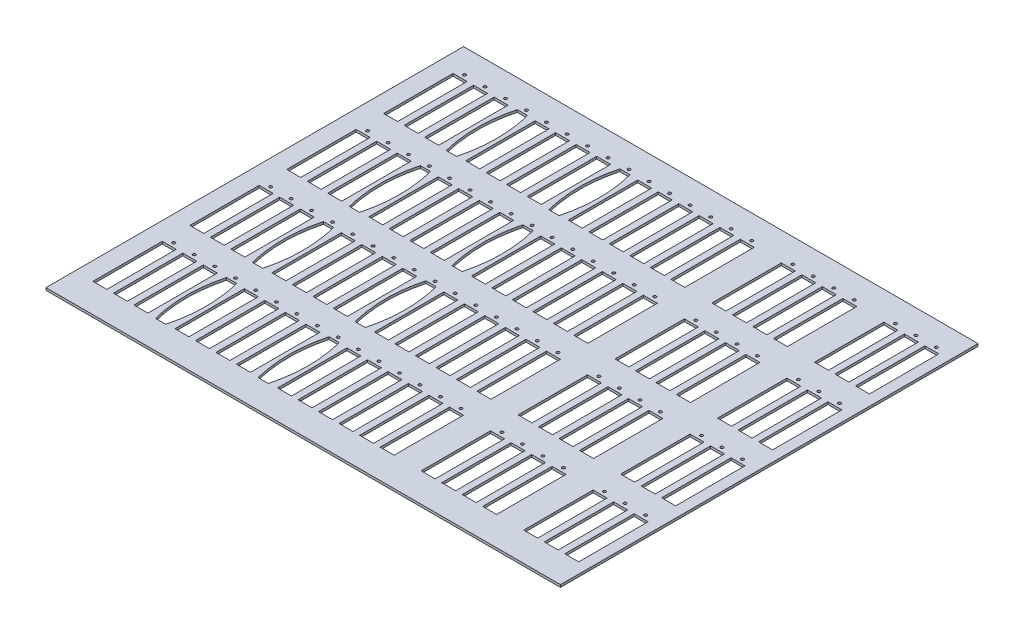
SolidWorks part; units mm, degrees
ref_plane "Front Plane" through (0, 0, 0) normal (0, 0, 1) x (1, 0, 0)
ref_plane "Top Plane" through (0, 0, 0) normal (0, 1, 0) x (1, 0, 0)
ref_plane "Right Plane" through (0, 0, 0) normal (1, 0, 0) x (0, 0, -1)
sketch "Sketch1" plane through (0, 0, 0) normal (0, 1, 0) x (1, 0, 0)
  line L1 (-337.058, -273.558) -> (337.058, -273.558)
  line L2 (-337.058, -273.558) -> (-337.058, 273.558)
  line L3 (-337.058, 273.558) -> (337.058, 273.558)
  line L4 (337.058, -273.558) -> (337.058, 273.558)
  line L5 (-337.058, -273.558) -> (337.058, 273.558) construction
  line L6 (-337.058, 273.558) -> (337.058, -273.558) construction
  point P0 (0, 0)
  dimension "D1" = 547.116
  dimension "D2" = 674.116
extrude "Boss-Extrude1" add sketch "Sketch1" along normal blind 3.175
sketch "Sketch2" plane through (0, 3.175, 0) normal (0, 1, 0) x (1, 0, 0)
  line L0 (327.406, 273.558) -> (327.406, -273.558) construction
  line L1 (337.058, 273.558) -> (-337.058, 273.558) construction
  line L2 (-337.058, -273.558) -> (337.058, -273.558) construction
  line L3 (337.058, -273.558) -> (337.058, 273.558) construction
  line L4 (-337.058, 273.558) -> (327.406, -273.558) construction
  line L5 (-337.058, 273.558) -> (-337.058, -273.558) construction
  line L6 (327.406, 254.254) -> (-317.754, 254.254) construction
  line L7 (327.406, 254.254) -> (327.406, -254.254) construction
  line L8 (327.406, -254.254) -> (-317.754, -254.254) construction
  line L9 (-317.754, 254.254) -> (-317.754, -254.254) construction
  line L10 (-304.3132, 254.254) -> (-304.3132, -254.254) construction
  line L11 (-223.6682, 254.254) -> (-223.6682, -254.254) construction
  line L12 (-317.754, 190.754) -> (327.406, 190.754) construction
  line L13 (-286.5755, 236.22) -> (-268.2875, 236.22)
  line L14 (-313.4572, 145.288) -> (-295.1692, 145.288)
  line L15 (-313.4572, 145.288) -> (-313.4572, 236.22)
  line L16 (-313.4572, 236.22) -> (-295.1692, 236.22)
  line L17 (-295.1692, 145.288) -> (-295.1692, 236.22)
  line L18 (-313.4572, 145.288) -> (-295.1692, 236.22) construction
  line L19 (-313.4572, 236.22) -> (-295.1692, 145.288) construction
  line L20 (-286.5755, 145.288) -> (-286.5755, 236.22)
  line L21 (-268.2875, 145.288) -> (-268.2875, 236.22)
  line L22 (-286.5755, 145.288) -> (-268.2875, 145.288)
  line L23 (-259.6938, 236.22) -> (-241.4058, 236.22)
  line L24 (-259.6938, 145.288) -> (-259.6938, 236.22)
  line L25 (-241.4058, 145.288) -> (-241.4058, 236.22)
  line L26 (-259.6938, 145.288) -> (-241.4058, 145.288)
  line L27 (-230.3357, 237.1725) -> (-217.0007, 237.1725)
  line L28 (-236.3682, 144.3355) -> (-210.9682, 144.3355) construction
  line L29 (-236.3682, 144.3355) -> (-236.3682, 237.1725) construction
  line L30 (-236.3682, 237.1725) -> (-210.9682, 237.1725) construction
  line L31 (-205.9305, 236.22) -> (-187.6425, 236.22)
  line L32 (-205.9305, 145.288) -> (-205.9305, 236.22)
  line L33 (-187.6425, 145.288) -> (-187.6425, 236.22)
  line L34 (-205.9305, 145.288) -> (-187.6425, 145.288)
  line L35 (-179.0488, 236.22) -> (-160.7608, 236.22)
  line L36 (-179.0488, 145.288) -> (-179.0488, 236.22)
  line L37 (-160.7608, 145.288) -> (-160.7608, 236.22)
  line L38 (-179.0488, 145.288) -> (-160.7608, 145.288)
  line L39 (-152.1672, 236.22) -> (-133.8792, 236.22)
  line L40 (-152.1672, 145.288) -> (-152.1672, 236.22)
  line L41 (-133.8792, 145.288) -> (-133.8792, 236.22)
  line L42 (-152.1672, 145.288) -> (-133.8792, 145.288)
  line L43 (-125.2855, 236.22) -> (-106.9975, 236.22)
  line L44 (-125.2855, 145.288) -> (-125.2855, 236.22)
  line L45 (-106.9975, 145.288) -> (-106.9975, 236.22)
  line L46 (-125.2855, 145.288) -> (-106.9975, 145.288)
  line L47 (-210.9682, 144.3355) -> (-210.9682, 237.1725) construction
  line L48 (-236.3682, 144.3355) -> (-210.9682, 237.1725) construction
  line L49 (-236.3682, 237.1725) -> (-210.9682, 144.3355) construction
  line L50 (-230.3357, 144.3355) -> (-217.0007, 144.3355)
  line L51 (-71.5222, 236.22) -> (-53.2342, 236.22)
  line L52 (-71.5222, 145.288) -> (-71.5222, 236.22)
  line L53 (-53.2342, 145.288) -> (-53.2342, 236.22)
  line L54 (-71.5222, 145.288) -> (-53.2342, 145.288)
  line L55 (-44.6405, 236.22) -> (-26.3525, 236.22)
  line L56 (-44.6405, 145.288) -> (-44.6405, 236.22)
  line L57 (-26.3525, 145.288) -> (-26.3525, 236.22)
  line L58 (-44.6405, 145.288) -> (-26.3525, 145.288)
  line L59 (-17.7588, 236.22) -> (0.5292, 236.22)
  line L60 (-17.7588, 145.288) -> (-17.7588, 236.22)
  line L61 (0.5292, 145.288) -> (0.5292, 236.22)
  line L62 (-17.7588, 145.288) -> (0.5292, 145.288)
  line L63 (9.1228, 236.22) -> (27.4108, 236.22)
  line L64 (9.1228, 145.288) -> (9.1228, 236.22)
  line L65 (27.4108, 145.288) -> (27.4108, 236.22)
  line L66 (9.1228, 145.288) -> (27.4108, 145.288)
  line L67 (36.0045, 236.22) -> (54.2925, 236.22)
  line L68 (36.0045, 145.288) -> (36.0045, 236.22)
  line L69 (54.2925, 145.288) -> (54.2925, 236.22)
  line L70 (36.0045, 145.288) -> (54.2925, 145.288)
  line L71 (62.8862, 236.22) -> (81.1742, 236.22)
  line L72 (62.8862, 145.288) -> (62.8862, 236.22)
  line L73 (81.1742, 145.288) -> (81.1742, 236.22)
  line L74 (62.8862, 145.288) -> (81.1742, 145.288)
  line L75 (-95.9273, 237.1725) -> (-82.5923, 237.1725)
  line L76 (-95.9273, 144.3355) -> (-82.5923, 144.3355)
  line L77 (-95.9273, 110.1725) -> (-82.5923, 110.1725)
  line L78 (-95.9273, 17.3355) -> (-82.5923, 17.3355)
  line L79 (116.6495, 236.22) -> (134.9375, 236.22)
  line L80 (116.6495, 145.288) -> (116.6495, 236.22)
  line L81 (134.9375, 145.288) -> (134.9375, 236.22)
  line L82 (116.6495, 145.288) -> (134.9375, 145.288)
  line L83 (143.5312, 236.22) -> (161.8192, 236.22)
  line L84 (143.5312, 145.288) -> (143.5312, 236.22)
  line L85 (161.8192, 145.288) -> (161.8192, 236.22)
  line L86 (143.5312, 145.288) -> (161.8192, 145.288)
  line L87 (170.4128, 236.22) -> (188.7008, 236.22)
  line L88 (170.4128, 145.288) -> (170.4128, 236.22)
  line L89 (188.7008, 145.288) -> (188.7008, 236.22)
  line L90 (170.4128, 145.288) -> (188.7008, 145.288)
  line L91 (197.2945, 236.22) -> (215.5825, 236.22)
  line L92 (197.2945, 145.288) -> (197.2945, 236.22)
  line L93 (215.5825, 145.288) -> (215.5825, 236.22)
  line L94 (197.2945, 145.288) -> (215.5825, 145.288)
  line L95 (-95.9273, -16.8275) -> (-82.5923, -16.8275)
  line L96 (-95.9273, -109.6645) -> (-82.5923, -109.6645)
  line L97 (-95.9273, -143.8275) -> (-82.5923, -143.8275)
  line L98 (-95.9273, -236.6645) -> (-82.5923, -236.6645)
  line L99 (251.0578, 236.22) -> (269.3458, 236.22)
  line L100 (251.0578, 145.288) -> (251.0578, 236.22)
  line L101 (269.3458, 145.288) -> (269.3458, 236.22)
  line L102 (251.0578, 145.288) -> (269.3458, 145.288)
  line L103 (277.9395, 236.22) -> (296.2275, 236.22)
  line L104 (277.9395, 145.288) -> (277.9395, 236.22)
  line L105 (296.2275, 145.288) -> (296.2275, 236.22)
  line L106 (277.9395, 145.288) -> (296.2275, 145.288)
  line L107 (304.8212, 236.22) -> (323.1092, 236.22)
  line L108 (304.8212, 145.288) -> (304.8212, 236.22)
  line L109 (323.1092, 145.288) -> (323.1092, 236.22)
  line L110 (304.8212, 145.288) -> (323.1092, 145.288)
  line L111 (-286.5755, 109.22) -> (-268.2875, 109.22)
  line L112 (-286.5755, 18.288) -> (-286.5755, 109.22)
  line L113 (-268.2875, 18.288) -> (-268.2875, 109.22)
  line L114 (-286.5755, 18.288) -> (-268.2875, 18.288)
  line L115 (-259.6938, 109.22) -> (-241.4058, 109.22)
  line L116 (-259.6938, 18.288) -> (-259.6938, 109.22)
  line L117 (-241.4058, 18.288) -> (-241.4058, 109.22)
  line L118 (-259.6938, 18.288) -> (-241.4058, 18.288)
  line L119 (-230.3357, 110.1725) -> (-217.0007, 110.1725)
  line L120 (-230.3357, 17.3355) -> (-217.0007, 17.3355)
  line L121 (-230.3357, -16.8275) -> (-217.0007, -16.8275)
  line L122 (-230.3357, -109.6645) -> (-217.0007, -109.6645)
  line L123 (-205.9305, 109.22) -> (-187.6425, 109.22)
  line L124 (-205.9305, 18.288) -> (-205.9305, 109.22)
  line L125 (-187.6425, 18.288) -> (-187.6425, 109.22)
  line L126 (-205.9305, 18.288) -> (-187.6425, 18.288)
  line L127 (-179.0488, 109.22) -> (-160.7608, 109.22)
  line L128 (-179.0488, 18.288) -> (-179.0488, 109.22)
  line L129 (-160.7608, 18.288) -> (-160.7608, 109.22)
  line L130 (-179.0488, 18.288) -> (-160.7608, 18.288)
  line L131 (-152.1672, 109.22) -> (-133.8792, 109.22)
  line L132 (-152.1672, 18.288) -> (-152.1672, 109.22)
  line L133 (-133.8792, 18.288) -> (-133.8792, 109.22)
  line L134 (-152.1672, 18.288) -> (-133.8792, 18.288)
  line L135 (-125.2855, 109.22) -> (-106.9975, 109.22)
  line L136 (-125.2855, 18.288) -> (-125.2855, 109.22)
  line L137 (-106.9975, 18.288) -> (-106.9975, 109.22)
  line L138 (-125.2855, 18.288) -> (-106.9975, 18.288)
  line L139 (-230.3357, -143.8275) -> (-217.0007, -143.8275)
  line L140 (-230.3357, -236.6645) -> (-217.0007, -236.6645)
  line L143 (-71.5222, 109.22) -> (-53.2342, 109.22)
  line L144 (-71.5222, 18.288) -> (-71.5222, 109.22)
  line L145 (-53.2342, 18.288) -> (-53.2342, 109.22)
  line L146 (-71.5222, 18.288) -> (-53.2342, 18.288)
  line L147 (-44.6405, 109.22) -> (-26.3525, 109.22)
  line L148 (-44.6405, 18.288) -> (-44.6405, 109.22)
  line L149 (-26.3525, 18.288) -> (-26.3525, 109.22)
  line L150 (-44.6405, 18.288) -> (-26.3525, 18.288)
  line L151 (-17.7588, 109.22) -> (0.5292, 109.22)
  line L152 (-17.7588, 18.288) -> (-17.7588, 109.22)
  line L153 (0.5292, 18.288) -> (0.5292, 109.22)
  line L154 (-17.7588, 18.288) -> (0.5292, 18.288)
  line L155 (9.1228, 109.22) -> (27.4108, 109.22)
  line L156 (9.1228, 18.288) -> (9.1228, 109.22)
  line L157 (27.4108, 18.288) -> (27.4108, 109.22)
  line L158 (9.1228, 18.288) -> (27.4108, 18.288)
  line L159 (36.0045, 109.22) -> (54.2925, 109.22)
  line L160 (36.0045, 18.288) -> (36.0045, 109.22)
  line L161 (54.2925, 18.288) -> (54.2925, 109.22)
  line L162 (36.0045, 18.288) -> (54.2925, 18.288)
  line L163 (62.8862, 109.22) -> (81.1742, 109.22)
  line L164 (62.8862, 18.288) -> (62.8862, 109.22)
  line L165 (81.1742, 18.288) -> (81.1742, 109.22)
  line L166 (62.8862, 18.288) -> (81.1742, 18.288)
  line L171 (116.6495, 109.22) -> (134.9375, 109.22)
  line L172 (116.6495, 18.288) -> (116.6495, 109.22)
  line L173 (134.9375, 18.288) -> (134.9375, 109.22)
  line L174 (116.6495, 18.288) -> (134.9375, 18.288)
  line L175 (143.5312, 109.22) -> (161.8192, 109.22)
  line L176 (143.5312, 18.288) -> (143.5312, 109.22)
  line L177 (161.8192, 18.288) -> (161.8192, 109.22)
  line L178 (143.5312, 18.288) -> (161.8192, 18.288)
  line L179 (170.4128, 109.22) -> (188.7008, 109.22)
  line L180 (170.4128, 18.288) -> (170.4128, 109.22)
  line L181 (188.7008, 18.288) -> (188.7008, 109.22)
  line L182 (170.4128, 18.288) -> (188.7008, 18.288)
  line L183 (197.2945, 109.22) -> (215.5825, 109.22)
  line L184 (197.2945, 18.288) -> (197.2945, 109.22)
  line L185 (215.5825, 18.288) -> (215.5825, 109.22)
  line L186 (197.2945, 18.288) -> (215.5825, 18.288)
  line L191 (251.0578, 109.22) -> (269.3458, 109.22)
  line L192 (251.0578, 18.288) -> (251.0578, 109.22)
  line L193 (269.3458, 18.288) -> (269.3458, 109.22)
  line L194 (251.0578, 18.288) -> (269.3458, 18.288)
  line L195 (277.9395, 109.22) -> (296.2275, 109.22)
  line L196 (277.9395, 18.288) -> (277.9395, 109.22)
  line L197 (296.2275, 18.288) -> (296.2275, 109.22)
  line L198 (277.9395, 18.288) -> (296.2275, 18.288)
  line L199 (304.8212, 109.22) -> (323.1092, 109.22)
  line L200 (304.8212, 18.288) -> (304.8212, 109.22)
  line L201 (323.1092, 18.288) -> (323.1092, 109.22)
  line L202 (304.8212, 18.288) -> (323.1092, 18.288)
  line L203 (-286.5755, -17.78) -> (-268.2875, -17.78)
  line L204 (-286.5755, -108.712) -> (-286.5755, -17.78)
  line L205 (-268.2875, -108.712) -> (-268.2875, -17.78)
  line L206 (-286.5755, -108.712) -> (-268.2875, -108.712)
  line L207 (-259.6938, -17.78) -> (-241.4058, -17.78)
  line L208 (-259.6938, -108.712) -> (-259.6938, -17.78)
  line L209 (-241.4058, -108.712) -> (-241.4058, -17.78)
  line L210 (-259.6938, -108.712) -> (-241.4058, -108.712)
  line L215 (-205.9305, -17.78) -> (-187.6425, -17.78)
  line L216 (-205.9305, -108.712) -> (-205.9305, -17.78)
  line L217 (-187.6425, -108.712) -> (-187.6425, -17.78)
  line L218 (-205.9305, -108.712) -> (-187.6425, -108.712)
  line L219 (-179.0488, -17.78) -> (-160.7608, -17.78)
  line L220 (-179.0488, -108.712) -> (-179.0488, -17.78)
  line L221 (-160.7608, -108.712) -> (-160.7608, -17.78)
  line L222 (-179.0488, -108.712) -> (-160.7608, -108.712)
  line L223 (-152.1672, -17.78) -> (-133.8792, -17.78)
  line L224 (-152.1672, -108.712) -> (-152.1672, -17.78)
  line L225 (-133.8792, -108.712) -> (-133.8792, -17.78)
  line L226 (-152.1672, -108.712) -> (-133.8792, -108.712)
  line L227 (-125.2855, -17.78) -> (-106.9975, -17.78)
  line L228 (-125.2855, -108.712) -> (-125.2855, -17.78)
  line L229 (-106.9975, -108.712) -> (-106.9975, -17.78)
  line L230 (-125.2855, -108.712) -> (-106.9975, -108.712)
  line L235 (-71.5222, -17.78) -> (-53.2342, -17.78)
  line L236 (-71.5222, -108.712) -> (-71.5222, -17.78)
  line L237 (-53.2342, -108.712) -> (-53.2342, -17.78)
  line L238 (-71.5222, -108.712) -> (-53.2342, -108.712)
  line L239 (-44.6405, -17.78) -> (-26.3525, -17.78)
  line L240 (-44.6405, -108.712) -> (-44.6405, -17.78)
  line L241 (-26.3525, -108.712) -> (-26.3525, -17.78)
  line L242 (-44.6405, -108.712) -> (-26.3525, -108.712)
  line L243 (-17.7588, -17.78) -> (0.5292, -17.78)
  line L244 (-17.7588, -108.712) -> (-17.7588, -17.78)
  line L245 (0.5292, -108.712) -> (0.5292, -17.78)
  line L246 (-17.7588, -108.712) -> (0.5292, -108.712)
  line L247 (9.1228, -17.78) -> (27.4108, -17.78)
  line L248 (9.1228, -108.712) -> (9.1228, -17.78)
  line L249 (27.4108, -108.712) -> (27.4108, -17.78)
  line L250 (9.1228, -108.712) -> (27.4108, -108.712)
  line L251 (36.0045, -17.78) -> (54.2925, -17.78)
  line L252 (36.0045, -108.712) -> (36.0045, -17.78)
  line L253 (54.2925, -108.712) -> (54.2925, -17.78)
  line L254 (36.0045, -108.712) -> (54.2925, -108.712)
  line L255 (62.8862, -17.78) -> (81.1742, -17.78)
  line L256 (62.8862, -108.712) -> (62.8862, -17.78)
  line L257 (81.1742, -108.712) -> (81.1742, -17.78)
  line L258 (62.8862, -108.712) -> (81.1742, -108.712)
  line L263 (116.6495, -17.78) -> (134.9375, -17.78)
  line L264 (116.6495, -108.712) -> (116.6495, -17.78)
  line L265 (134.9375, -108.712) -> (134.9375, -17.78)
  line L266 (116.6495, -108.712) -> (134.9375, -108.712)
  line L267 (143.5312, -17.78) -> (161.8192, -17.78)
  line L268 (143.5312, -108.712) -> (143.5312, -17.78)
  line L269 (161.8192, -108.712) -> (161.8192, -17.78)
  line L270 (143.5312, -108.712) -> (161.8192, -108.712)
  line L271 (170.4128, -17.78) -> (188.7008, -17.78)
  line L272 (170.4128, -108.712) -> (170.4128, -17.78)
  line L273 (188.7008, -108.712) -> (188.7008, -17.78)
  line L274 (170.4128, -108.712) -> (188.7008, -108.712)
  line L275 (197.2945, -17.78) -> (215.5825, -17.78)
  line L276 (197.2945, -108.712) -> (197.2945, -17.78)
  line L277 (215.5825, -108.712) -> (215.5825, -17.78)
  line L278 (197.2945, -108.712) -> (215.5825, -108.712)
  line L283 (251.0578, -17.78) -> (269.3458, -17.78)
  line L284 (251.0578, -108.712) -> (251.0578, -17.78)
  line L285 (269.3458, -108.712) -> (269.3458, -17.78)
  line L286 (251.0578, -108.712) -> (269.3458, -108.712)
  line L287 (277.9395, -17.78) -> (296.2275, -17.78)
  line L288 (277.9395, -108.712) -> (277.9395, -17.78)
  line L289 (296.2275, -108.712) -> (296.2275, -17.78)
  line L290 (277.9395, -108.712) -> (296.2275, -108.712)
  line L291 (304.8212, -17.78) -> (323.1092, -17.78)
  line L292 (304.8212, -108.712) -> (304.8212, -17.78)
  line L293 (323.1092, -108.712) -> (323.1092, -17.78)
  line L294 (304.8212, -108.712) -> (323.1092, -108.712)
  line L295 (-286.5755, -144.78) -> (-268.2875, -144.78)
  line L296 (-286.5755, -235.712) -> (-286.5755, -144.78)
  line L297 (-268.2875, -235.712) -> (-268.2875, -144.78)
  line L298 (-286.5755, -235.712) -> (-268.2875, -235.712)
  line L299 (-259.6938, -144.78) -> (-241.4058, -144.78)
  line L300 (-259.6938, -235.712) -> (-259.6938, -144.78)
  line L301 (-241.4058, -235.712) -> (-241.4058, -144.78)
  line L302 (-259.6938, -235.712) -> (-241.4058, -235.712)
  line L307 (-205.9305, -144.78) -> (-187.6425, -144.78)
  line L308 (-205.9305, -235.712) -> (-205.9305, -144.78)
  line L309 (-187.6425, -235.712) -> (-187.6425, -144.78)
  line L310 (-205.9305, -235.712) -> (-187.6425, -235.712)
  line L311 (-179.0488, -144.78) -> (-160.7608, -144.78)
  line L312 (-179.0488, -235.712) -> (-179.0488, -144.78)
  line L313 (-160.7608, -235.712) -> (-160.7608, -144.78)
  line L314 (-179.0488, -235.712) -> (-160.7608, -235.712)
  line L315 (-152.1672, -144.78) -> (-133.8792, -144.78)
  line L316 (-152.1672, -235.712) -> (-152.1672, -144.78)
  line L317 (-133.8792, -235.712) -> (-133.8792, -144.78)
  line L318 (-152.1672, -235.712) -> (-133.8792, -235.712)
  line L319 (-125.2855, -144.78) -> (-106.9975, -144.78)
  line L320 (-125.2855, -235.712) -> (-125.2855, -144.78)
  line L321 (-106.9975, -235.712) -> (-106.9975, -144.78)
  line L322 (-125.2855, -235.712) -> (-106.9975, -235.712)
  line L327 (-71.5222, -144.78) -> (-53.2342, -144.78)
  line L328 (-71.5222, -235.712) -> (-71.5222, -144.78)
  line L329 (-53.2342, -235.712) -> (-53.2342, -144.78)
  line L330 (-71.5222, -235.712) -> (-53.2342, -235.712)
  line L331 (-44.6405, -144.78) -> (-26.3525, -144.78)
  line L332 (-44.6405, -235.712) -> (-44.6405, -144.78)
  line L333 (-26.3525, -235.712) -> (-26.3525, -144.78)
  line L334 (-44.6405, -235.712) -> (-26.3525, -235.712)
  line L335 (-17.7588, -144.78) -> (0.5292, -144.78)
  line L336 (-17.7588, -235.712) -> (-17.7588, -144.78)
  line L337 (0.5292, -235.712) -> (0.5292, -144.78)
  line L338 (-17.7588, -235.712) -> (0.5292, -235.712)
  line L339 (9.1228, -144.78) -> (27.4108, -144.78)
  line L340 (9.1228, -235.712) -> (9.1228, -144.78)
  line L341 (27.4108, -235.712) -> (27.4108, -144.78)
  line L342 (9.1228, -235.712) -> (27.4108, -235.712)
  line L343 (36.0045, -144.78) -> (54.2925, -144.78)
  line L344 (36.0045, -235.712) -> (36.0045, -144.78)
  line L345 (54.2925, -235.712) -> (54.2925, -144.78)
  line L346 (36.0045, -235.712) -> (54.2925, -235.712)
  line L347 (62.8862, -144.78) -> (81.1742, -144.78)
  line L348 (62.8862, -235.712) -> (62.8862, -144.78)
  line L349 (81.1742, -235.712) -> (81.1742, -144.78)
  line L350 (62.8862, -235.712) -> (81.1742, -235.712)
  line L355 (116.6495, -144.78) -> (134.9375, -144.78)
  line L356 (116.6495, -235.712) -> (116.6495, -144.78)
  line L357 (134.9375, -235.712) -> (134.9375, -144.78)
  line L358 (116.6495, -235.712) -> (134.9375, -235.712)
  line L359 (143.5312, -144.78) -> (161.8192, -144.78)
  line L360 (143.5312, -235.712) -> (143.5312, -144.78)
  line L361 (161.8192, -235.712) -> (161.8192, -144.78)
  line L362 (143.5312, -235.712) -> (161.8192, -235.712)
  line L363 (170.4128, -144.78) -> (188.7008, -144.78)
  line L364 (170.4128, -235.712) -> (170.4128, -144.78)
  line L365 (188.7008, -235.712) -> (188.7008, -144.78)
  line L366 (170.4128, -235.712) -> (188.7008, -235.712)
  line L367 (197.2945, -144.78) -> (215.5825, -144.78)
  line L368 (197.2945, -235.712) -> (197.2945, -144.78)
  line L369 (215.5825, -235.712) -> (215.5825, -144.78)
  line L370 (197.2945, -235.712) -> (215.5825, -235.712)
  line L375 (251.0578, -144.78) -> (269.3458, -144.78)
  line L376 (251.0578, -235.712) -> (251.0578, -144.78)
  line L377 (269.3458, -235.712) -> (269.3458, -144.78)
  line L378 (251.0578, -235.712) -> (269.3458, -235.712)
  line L379 (277.9395, -144.78) -> (296.2275, -144.78)
  line L380 (277.9395, -235.712) -> (277.9395, -144.78)
  line L381 (296.2275, -235.712) -> (296.2275, -144.78)
  line L382 (277.9395, -235.712) -> (296.2275, -235.712)
  line L383 (304.8212, -144.78) -> (323.1092, -144.78)
  line L384 (304.8212, -235.712) -> (304.8212, -144.78)
  line L385 (323.1092, -235.712) -> (323.1092, -144.78)
  line L386 (304.8212, -235.712) -> (323.1092, -235.712)
  line L387 (-313.4572, 109.22) -> (-295.1692, 109.22)
  line L388 (-313.4572, 18.288) -> (-313.4572, 109.22)
  line L389 (-295.1692, 18.288) -> (-295.1692, 109.22)
  line L390 (-313.4572, 18.288) -> (-295.1692, 18.288)
  line L391 (-313.4572, -17.78) -> (-295.1692, -17.78)
  line L392 (-313.4572, -108.712) -> (-313.4572, -17.78)
  line L393 (-295.1692, -108.712) -> (-295.1692, -17.78)
  line L394 (-313.4572, -108.712) -> (-295.1692, -108.712)
  line L395 (-313.4572, -144.78) -> (-295.1692, -144.78)
  line L396 (-313.4572, -235.712) -> (-313.4572, -144.78)
  line L397 (-295.1692, -235.712) -> (-295.1692, -144.78)
  line L398 (-313.4572, -235.712) -> (-295.1692, -235.712)
  line L399 (-232.8122, 236.22) -> (-214.5242, 236.22) [skipped]
  line L400 (-232.8122, 145.288) -> (-232.8122, 236.22) [skipped]
  line L401 (-214.5242, 145.288) -> (-214.5242, 236.22) [skipped]
  line L402 (-232.8122, 145.288) -> (-214.5242, 145.288) [skipped]
  line L403 (-232.8122, 109.22) -> (-214.5242, 109.22) [skipped]
  line L404 (-232.8122, 18.288) -> (-232.8122, 109.22) [skipped]
  line L405 (-214.5242, 18.288) -> (-214.5242, 109.22) [skipped]
  line L406 (-232.8122, 18.288) -> (-214.5242, 18.288) [skipped]
  line L407 (-232.8122, -17.78) -> (-214.5242, -17.78) [skipped]
  line L408 (-232.8122, -108.712) -> (-232.8122, -17.78) [skipped]
  line L409 (-214.5242, -108.712) -> (-214.5242, -17.78) [skipped]
  line L410 (-232.8122, -108.712) -> (-214.5242, -108.712) [skipped]
  line L411 (-232.8122, -144.78) -> (-214.5242, -144.78) [skipped]
  line L412 (-232.8122, -235.712) -> (-232.8122, -144.78) [skipped]
  line L413 (-214.5242, -235.712) -> (-214.5242, -144.78) [skipped]
  line L414 (-232.8122, -235.712) -> (-214.5242, -235.712) [skipped]
  line L415 (-98.4038, 236.22) -> (-80.1158, 236.22) [skipped]
  line L416 (-98.4038, 145.288) -> (-98.4038, 236.22) [skipped]
  line L417 (-80.1158, 145.288) -> (-80.1158, 236.22) [skipped]
  line L418 (-98.4038, 145.288) -> (-80.1158, 145.288) [skipped]
  line L419 (-98.4038, 109.22) -> (-80.1158, 109.22) [skipped]
  line L420 (-98.4038, 18.288) -> (-98.4038, 109.22) [skipped]
  line L421 (-80.1158, 18.288) -> (-80.1158, 109.22) [skipped]
  line L422 (-98.4038, 18.288) -> (-80.1158, 18.288) [skipped]
  line L423 (-98.4038, -17.78) -> (-80.1158, -17.78) [skipped]
  line L424 (-98.4038, -108.712) -> (-98.4038, -17.78) [skipped]
  line L425 (-80.1158, -108.712) -> (-80.1158, -17.78) [skipped]
  line L426 (-98.4038, -108.712) -> (-80.1158, -108.712) [skipped]
  line L427 (-98.4038, -144.78) -> (-80.1158, -144.78) [skipped]
  line L428 (-98.4038, -235.712) -> (-98.4038, -144.78) [skipped]
  line L429 (-80.1158, -235.712) -> (-80.1158, -144.78) [skipped]
  line L430 (-98.4038, -235.712) -> (-80.1158, -235.712) [skipped]
  line L431 (224.1762, 236.22) -> (242.4642, 236.22) [skipped]
  line L432 (224.1762, 145.288) -> (224.1762, 236.22) [skipped]
  line L433 (242.4642, 145.288) -> (242.4642, 236.22) [skipped]
  line L434 (224.1762, 145.288) -> (242.4642, 145.288) [skipped]
  line L435 (224.1762, 109.22) -> (242.4642, 109.22) [skipped]
  line L436 (224.1762, 18.288) -> (224.1762, 109.22) [skipped]
  line L437 (242.4642, 18.288) -> (242.4642, 109.22) [skipped]
  line L438 (224.1762, 18.288) -> (242.4642, 18.288) [skipped]
  line L439 (224.1762, -17.78) -> (242.4642, -17.78) [skipped]
  line L440 (224.1762, -108.712) -> (224.1762, -17.78) [skipped]
  line L441 (242.4642, -108.712) -> (242.4642, -17.78) [skipped]
  line L442 (224.1762, -108.712) -> (242.4642, -108.712) [skipped]
  line L443 (224.1762, -144.78) -> (242.4642, -144.78) [skipped]
  line L444 (224.1762, -235.712) -> (224.1762, -144.78) [skipped]
  line L445 (242.4642, -235.712) -> (242.4642, -144.78) [skipped]
  line L446 (224.1762, -235.712) -> (242.4642, -235.712) [skipped]
  line L447 (89.7678, 236.22) -> (108.0558, 236.22) [skipped]
  line L448 (89.7678, 145.288) -> (89.7678, 236.22) [skipped]
  line L449 (108.0558, 145.288) -> (108.0558, 236.22) [skipped]
  line L450 (89.7678, 145.288) -> (108.0558, 145.288) [skipped]
  line L451 (89.7678, 109.22) -> (108.0558, 109.22) [skipped]
  line L452 (89.7678, 18.288) -> (89.7678, 109.22) [skipped]
  line L453 (108.0558, 18.288) -> (108.0558, 109.22) [skipped]
  line L454 (89.7678, 18.288) -> (108.0558, 18.288) [skipped]
  line L455 (89.7678, -17.78) -> (108.0558, -17.78) [skipped]
  line L456 (89.7678, -108.712) -> (89.7678, -17.78) [skipped]
  line L457 (108.0558, -108.712) -> (108.0558, -17.78) [skipped]
  line L458 (89.7678, -108.712) -> (108.0558, -108.712) [skipped]
  line L459 (89.7678, -144.78) -> (108.0558, -144.78) [skipped]
  line L460 (89.7678, -235.712) -> (89.7678, -144.78) [skipped]
  line L461 (108.0558, -235.712) -> (108.0558, -144.78) [skipped]
  line L462 (89.7678, -235.712) -> (108.0558, -235.712) [skipped]
  circle A0 centre (-304.3132, 242.062) radius 1.905
  circle A1 centre (-277.4315, 242.062) radius 1.905
  circle A2 centre (-250.5498, 242.062) radius 1.905
  circle A3 centre (-223.6682, 242.5065) radius 1.905
  circle A4 centre (-196.7865, 242.062) radius 1.905
  circle A5 centre (-169.9048, 242.062) radius 1.905
  circle A6 centre (-143.0232, 242.062) radius 1.905
  circle A7 centre (-116.1415, 242.062) radius 1.905
  circle A8 centre (-89.2598, 242.5065) radius 1.905
  circle A9 centre (-62.3782, 242.062) radius 1.905
  circle A10 centre (-35.4965, 242.062) radius 1.905
  circle A11 centre (-8.6148, 242.062) radius 1.905
  circle A12 centre (18.2668, 242.062) radius 1.905
  circle A13 centre (45.1485, 242.062) radius 1.905
  circle A14 centre (72.0302, 242.062) radius 1.905
  circle A15 centre (-89.2598, 115.5065) radius 1.905
  circle A16 centre (125.7935, 242.062) radius 1.905
  circle A17 centre (152.6752, 242.062) radius 1.905
  circle A18 centre (179.5568, 242.062) radius 1.905
  circle A19 centre (206.4385, 242.062) radius 1.905
  circle A20 centre (-89.2598, -11.4935) radius 1.905
  circle A21 centre (260.2018, 242.062) radius 1.905
  circle A22 centre (287.0835, 242.062) radius 1.905
  circle A23 centre (313.9652, 242.062) radius 1.905
  circle A24 centre (-277.4315, 115.062) radius 1.905
  circle A25 centre (-250.5498, 115.062) radius 1.905
  circle A26 centre (-89.2598, -138.4935) radius 1.905
  circle A27 centre (-196.7865, 115.062) radius 1.905
  circle A28 centre (-169.9048, 115.062) radius 1.905
  circle A29 centre (-143.0232, 115.062) radius 1.905
  circle A30 centre (-116.1415, 115.062) radius 1.905
  circle A31 centre (-223.6682, 115.5065) radius 1.905
  circle A32 centre (-62.3782, 115.062) radius 1.905
  circle A33 centre (-35.4965, 115.062) radius 1.905
  circle A34 centre (-8.6148, 115.062) radius 1.905
  circle A35 centre (18.2668, 115.062) radius 1.905
  circle A36 centre (45.1485, 115.062) radius 1.905
  circle A37 centre (72.0302, 115.062) radius 1.905
  circle A38 centre (-223.6682, -11.4935) radius 1.905
  circle A39 centre (125.7935, 115.062) radius 1.905
  circle A40 centre (152.6752, 115.062) radius 1.905
  circle A41 centre (179.5568, 115.062) radius 1.905
  circle A42 centre (206.4385, 115.062) radius 1.905
  circle A43 centre (-223.6682, -138.4935) radius 1.905
  circle A44 centre (260.2018, 115.062) radius 1.905
  circle A45 centre (287.0835, 115.062) radius 1.905
  circle A46 centre (313.9652, 115.062) radius 1.905
  circle A47 centre (-277.4315, -11.938) radius 1.905
  circle A48 centre (-250.5498, -11.938) radius 1.905
  circle A50 centre (-196.7865, -11.938) radius 1.905
  circle A51 centre (-169.9048, -11.938) radius 1.905
  circle A52 centre (-143.0232, -11.938) radius 1.905
  circle A53 centre (-116.1415, -11.938) radius 1.905
  circle A55 centre (-62.3782, -11.938) radius 1.905
  circle A56 centre (-35.4965, -11.938) radius 1.905
  circle A57 centre (-8.6148, -11.938) radius 1.905
  circle A58 centre (18.2668, -11.938) radius 1.905
  circle A59 centre (45.1485, -11.938) radius 1.905
  circle A60 centre (72.0302, -11.938) radius 1.905
  circle A62 centre (125.7935, -11.938) radius 1.905
  circle A63 centre (152.6752, -11.938) radius 1.905
  circle A64 centre (179.5568, -11.938) radius 1.905
  circle A65 centre (206.4385, -11.938) radius 1.905
  circle A67 centre (260.2018, -11.938) radius 1.905
  circle A68 centre (287.0835, -11.938) radius 1.905
  circle A69 centre (313.9652, -11.938) radius 1.905
  circle A70 centre (-277.4315, -138.938) radius 1.905
  circle A71 centre (-250.5498, -138.938) radius 1.905
  circle A73 centre (-196.7865, -138.938) radius 1.905
  circle A74 centre (-169.9048, -138.938) radius 1.905
  circle A75 centre (-143.0232, -138.938) radius 1.905
  circle A76 centre (-116.1415, -138.938) radius 1.905
  circle A78 centre (-62.3782, -138.938) radius 1.905
  circle A79 centre (-35.4965, -138.938) radius 1.905
  circle A80 centre (-8.6148, -138.938) radius 1.905
  circle A81 centre (18.2668, -138.938) radius 1.905
  circle A82 centre (45.1485, -138.938) radius 1.905
  circle A83 centre (72.0302, -138.938) radius 1.905
  circle A85 centre (125.7935, -138.938) radius 1.905
  circle A86 centre (152.6752, -138.938) radius 1.905
  circle A87 centre (179.5568, -138.938) radius 1.905
  circle A88 centre (206.4385, -138.938) radius 1.905
  circle A90 centre (260.2018, -138.938) radius 1.905
  circle A91 centre (287.0835, -138.938) radius 1.905
  circle A92 centre (313.9652, -138.938) radius 1.905
  circle A93 centre (-304.3132, 115.062) radius 1.905
  circle A94 centre (-304.3132, -11.938) radius 1.905
  circle A95 centre (-304.3132, -138.938) radius 1.905
  circle A96 centre (-223.6682, 242.062) radius 1.905 [skipped]
  circle A97 centre (-223.6682, 115.062) radius 1.905 [skipped]
  circle A98 centre (-223.6682, -11.938) radius 1.905 [skipped]
  circle A99 centre (-223.6682, -138.938) radius 1.905 [skipped]
  circle A100 centre (-89.2598, 242.062) radius 1.905 [skipped]
  circle A101 centre (-89.2598, 115.062) radius 1.905 [skipped]
  circle A102 centre (-89.2598, -11.938) radius 1.905 [skipped]
  circle A103 centre (-89.2598, -138.938) radius 1.905 [skipped]
  circle A104 centre (233.3202, 242.062) radius 1.905 [skipped]
  circle A105 centre (233.3202, 115.062) radius 1.905 [skipped]
  circle A106 centre (233.3202, -11.938) radius 1.905 [skipped]
  circle A107 centre (233.3202, -138.938) radius 1.905 [skipped]
  circle A108 centre (98.9118, 242.062) radius 1.905 [skipped]
  circle A109 centre (98.9118, 115.062) radius 1.905 [skipped]
  circle A110 centre (98.9118, -11.938) radius 1.905 [skipped]
  circle A111 centre (98.9118, -138.938) radius 1.905 [skipped]
  spline S0 degree 2 poles (-217.0007, 237.1725) (-204.9357, 190.754) (-217.0007, 144.3355) knots 0 0 0 1 1 1
  spline S1 degree 2 poles (-230.3357, 237.1725) (-242.4007, 190.754) (-230.3357, 144.3355) knots 0 0 0 1 1 1
  spline S2 degree 2 poles (-95.9273, 237.1725) (-107.9923, 190.754) (-95.9273, 144.3355) knots 0 0 0 1 1 1
  spline S3 degree 2 poles (-82.5923, 237.1725) (-70.5273, 190.754) (-82.5923, 144.3355) knots 0 0 0 1 1 1
  spline S4 degree 2 poles (-95.9273, 110.1725) (-107.9923, 63.754) (-95.9273, 17.3355) knots 0 0 0 1 1 1
  spline S5 degree 2 poles (-82.5923, 110.1725) (-70.5273, 63.754) (-82.5923, 17.3355) knots 0 0 0 1 1 1
  spline S6 degree 2 poles (-95.9273, -16.8275) (-107.9923, -63.246) (-95.9273, -109.6645) knots 0 0 0 1 1 1
  spline S7 degree 2 poles (-82.5923, -16.8275) (-70.5273, -63.246) (-82.5923, -109.6645) knots 0 0 0 1 1 1
  spline S8 degree 2 poles (-95.9273, -143.8275) (-107.9923, -190.246) (-95.9273, -236.6645) knots 0 0 0 1 1 1
  spline S9 degree 2 poles (-82.5923, -143.8275) (-70.5273, -190.246) (-82.5923, -236.6645) knots 0 0 0 1 1 1
  spline S10 degree 2 poles (-230.3357, 110.1725) (-242.4007, 63.754) (-230.3357, 17.3355) knots 0 0 0 1 1 1
  spline S11 degree 2 poles (-217.0007, 110.1725) (-204.9357, 63.754) (-217.0007, 17.3355) knots 0 0 0 1 1 1
  spline S12 degree 2 poles (-230.3357, -16.8275) (-242.4007, -63.246) (-230.3357, -109.6645) knots 0 0 0 1 1 1
  spline S13 degree 2 poles (-217.0007, -16.8275) (-204.9357, -63.246) (-217.0007, -109.6645) knots 0 0 0 1 1 1
  spline S14 degree 2 poles (-230.3357, -143.8275) (-242.4007, -190.246) (-230.3357, -236.6645) knots 0 0 0 1 1 1
  spline S15 degree 2 poles (-217.0007, -143.8275) (-204.9357, -190.246) (-217.0007, -236.6645) knots 0 0 0 1 1 1
  point P22 (-304.3132, 190.754)
  point P29 (-223.6682, 190.754)
  point P49 (-223.6682, 237.1725)
  point P76 (-223.6682, 144.3355)
  dimension "D10" = 3.81
  dimension "D11" = 5.842
  dimension "D19" = 5.334
  dimension "D20" = 3.81
  dimension "D1" = 9.652
  dimension "D2" = 19.304
  dimension "D3" = 19.304
  dimension "D4" = 19.304
  dimension "D5" = 13.4408
  dimension "D7" = 63.5
  dimension "D8" = 90.932
  dimension "D9" = 18.288
  dimension "D12" = 560.7262
  dimension "D15" = 158.496
  dimension "D16" = 25.4
  dimension "D17" = 92.837
  dimension "D18" = 13.335
  dimension "D23" = 413.6178
  dimension "D24" = 439.0178
  dimension "D25" = 158.0515
  dimension "D26" = 209.804
  dimension "D27" = 336.804
  dimension "D28" = 463.804
  dimension "D6" = 2
  dimension "D13" = 24
  dimension "D14" = 4
  dimension "D21" = 2
  dimension "D22" = 4
extrude "Cut-Extrude1" cut sketch "Sketch2" against normal blind 3.175
